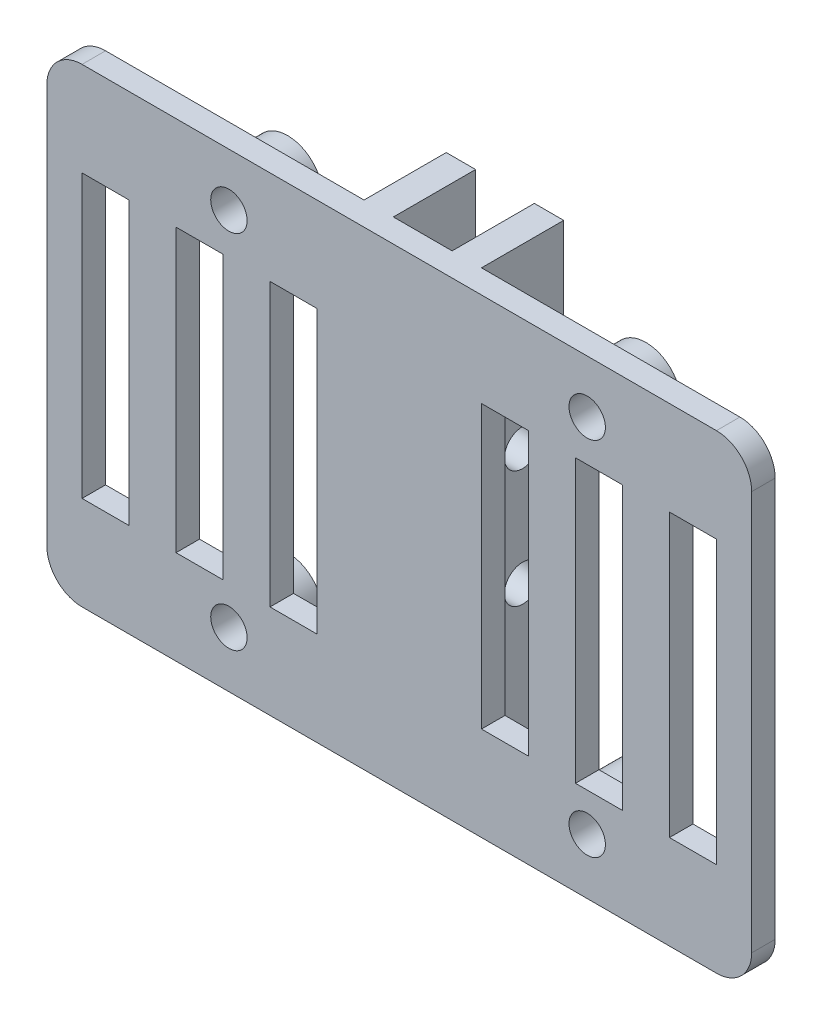
SolidWorks part; units mm, degrees
ref_plane "Plan de face" through (0, 0, 0) normal (0, 0, 1) x (1, 0, 0)
ref_plane "Plan de dessus" through (0, 0, 0) normal (0, 1, 0) x (1, 0, 0)
ref_plane "Plan de droite" through (0, 0, 0) normal (1, 0, 0) x (0, 0, -1)
sketch "Esquisse1" plane through (0, 0, 0) normal (0, 0, 1) x (1, 0, 0)
  line L1 (0, 0) -> (60, 0)
  line L2 (0, 0) -> (0, 40)
  line L3 (0, 40) -> (60, 40)
  line L4 (60, 0) -> (60, 40)
extrude "Boss.-Extru.1" add sketch "Esquisse1" along normal blind 9
sketch "Esquisse2" plane through (0, 0, 0) normal (0, 0, -1) x (-1, 0, 0)
  line L1 (-25, 40) -> (0, 40)
  line L2 (-25, 40) -> (-25, 0)
  line L3 (-25, 0) -> (0, 0)
  line L4 (0, 40) -> (0, 0)
  line L5 (-60, 40) -> (-35, 40)
  line L6 (-60, 40) -> (-60, 0)
  line L7 (-60, 0) -> (-35, 0)
  line L8 (-35, 40) -> (-35, 0)
  line L9 (-27.5, 40) -> (-32.5, 40)
  line L10 (-27.5, 40) -> (-27.5, 0)
  line L11 (-27.5, 0) -> (-32.5, 0)
  line L12 (-32.5, 40) -> (-32.5, 0)
  point P12 (0, 0)
  point P13 (0, 0)
  point P14 (0, 0)
  point P15 (0, 0)
  point P16 (0, 0)
  point P17 (0, 0)
  point P18 (0, 0)
  point P19 (0, 0)
  point P20 (0, 0)
  point P21 (0, 0)
  point P22 (0, 0)
  point P23 (0, 0)
  point P24 (0, 0)
  point P25 (0, 0)
  point P26 (0, 0)
  point P27 (0, 0)
  point P28 (0, 0)
extrude "Enlèv. mat.-Extru.1" cut sketch "Esquisse2" against normal blind 7
sketch "Esquisse3" plane through (35, 0, 0) normal (1, 0, 0) x (0, 0, -1)
  circle A0 centre (-3.5, 15) radius 1.55
  circle A1 centre (-3.5, 25) radius 1.55
  point P2 (0, 0)
  point P5 (-3.5655, 34.6493)
  point P6 (0, 0)
  point P7 (0, 0)
  point P8 (0, 0)
  point P9 (0, 0)
  point P10 (0, 0)
extrude "Enlèv. mat.-Extru.2" cut sketch "Esquisse3" against normal through all
fillet "Congé1" radius 3 4 edges at (0, 0, 8) (60, 0, 8) (0, 40, 8) (60, 40, 8)
sketch "Esquisse9" plane through (0, 0, 7) normal (0, 0, -1) x (-1, 0, 0)
  circle A1 centre (-46, 35.5) radius 3
  circle A2 centre (-15.5, 35.5) radius 3
  circle A3 centre (-15.5, 4.75) radius 3
  circle A4 centre (-46, 4.75) radius 3
extrude "Boss.-Extru.2" add sketch "Esquisse9" along normal blind 3
sketch "Esquisse5" plane through (0, 0, 7) normal (0, 0, -1) x (-1, 0, 0)
  circle A0 centre (-46, 35.5) radius 1.55
  circle A1 centre (-46, 4.75) radius 1.55
  circle A2 centre (-15.5, 4.75) radius 1.55
  circle A3 centre (-15.5, 35.5) radius 1.55
  point P8 (-13.6254, 1.6184)
  point P9 (-17.0023, 37.8719)
  point P10 (-45.6737, 1.8095)
  point P11 (0, 0)
  point P12 (0, 0)
  point P13 (0, 0)
  point P14 (0, 0)
  point P15 (0, 0)
  point P16 (0, 0)
  point P17 (0, 0)
  point P18 (0, 0)
  point P19 (0, 0)
  point P20 (0, 0)
  point P21 (0, 0)
  point P22 (0, 0)
  point P23 (0, 0)
  point P24 (0, 0)
  point P25 (0, 0)
  point P26 (0, 0)
  point P27 (0, 0)
  point P28 (0, 0)
  point P29 (0, 0)
  point P30 (0, 0)
  point P31 (0, 0)
  point P32 (0, 0)
  point P33 (0, 0)
  point P34 (0, 0)
  point P35 (0, 0)
  point P36 (0, 0)
  point P37 (0, 0)
  point P38 (0, 0)
  point P39 (0, 0)
  point P40 (0, 0)
  point P41 (0, 0)
  point P42 (0, 0)
  point P43 (0, 0)
  point P44 (0, 0)
  point P45 (0, 0)
  point P46 (0, 0)
  point P47 (0, 0)
  point P48 (0, 0)
  point P49 (0, 0)
  point P50 (0, 0)
  point P51 (0, 0)
  point P52 (0, 0)
extrude "Enlèv. mat.-Extru.4" cut sketch "Esquisse5" against normal through all both and the other way through all
sketch "Esquisse6" plane through (0, 0, 7) normal (0, 0, -1) x (-1, 0, 0)
  line L0 (-49, 32) -> (-45, 32)
  line L1 (-57, 32) -> (-53, 32)
  line L2 (-57, 32) -> (-57, 8)
  line L3 (-57, 8) -> (-53, 8)
  line L4 (-53, 32) -> (-53, 8)
  line L5 (-49, 32) -> (-49, 8)
  line L6 (-45, 32) -> (-45, 8)
  line L7 (-49, 8) -> (-45, 8)
  line L8 (-41, 32) -> (-37, 32)
  line L9 (-41, 32) -> (-41, 8)
  line L10 (-37, 32) -> (-37, 8)
  line L11 (-41, 8) -> (-37, 8)
  dimension "D1" = 3
sketch "Esquisse8" plane through (0, 0, 7) normal (0, 0, -1) x (-1, 0, 0)
  line L0 (-11, 32) -> (-11, 8)
  line L1 (-3, 32) -> (-7, 32)
  line L2 (-3, 32) -> (-3, 8)
  line L3 (-3, 8) -> (-7, 8)
  line L4 (-7, 32) -> (-7, 8)
  line L5 (-11, 32) -> (-15, 32)
  line L6 (-15, 32) -> (-15, 8)
  line L7 (-11, 8) -> (-15, 8)
  line L8 (-19, 32) -> (-19, 8)
  line L9 (-19, 32) -> (-23, 32)
  line L10 (-23, 32) -> (-23, 8)
  line L11 (-19, 8) -> (-23, 8)
  dimension "D1" = 3
extrude "Enlèv. mat.-Extru.5" cut sketch "Esquisse8" against normal blind 7
extrude "Enlèv. mat.-Extru.6" cut sketch "Esquisse6" against normal blind 7
